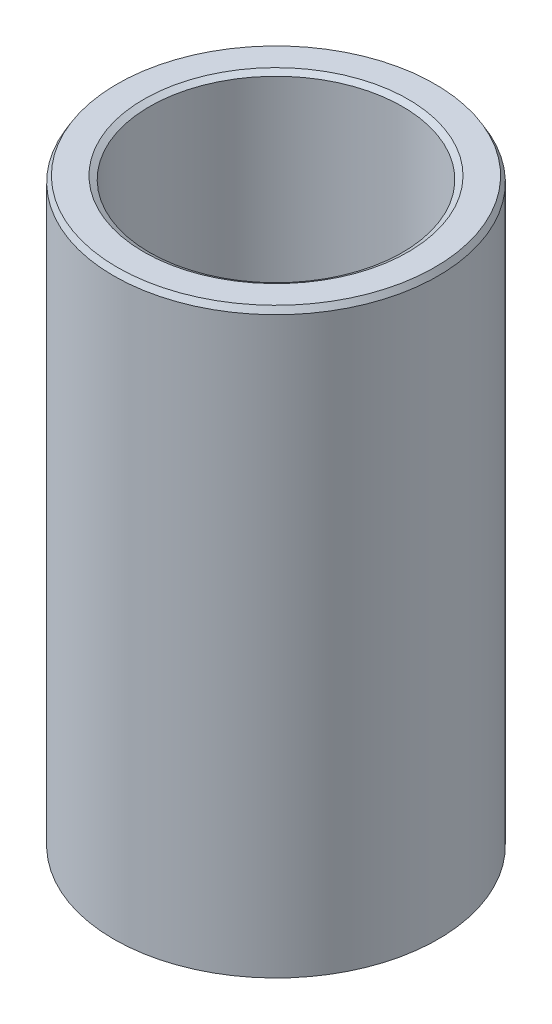
SolidWorks part; units mm, degrees
ref_plane "Front Plane" through (0, 0, 0) normal (0, 0, 1) x (1, 0, 0)
ref_plane "Top Plane" through (0, 0, 0) normal (0, 1, 0) x (1, 0, 0)
ref_plane "Right Plane" through (0, 0, 0) normal (1, 0, 0) x (0, 0, -1)
sketch "Sketch1" plane through (0, 0, 0) normal (0, 1, 0) x (1, 0, 0)
  circle A0 centre (0, 0) radius 47.5
  dimension "SLEEVE_OD" = 95
extrude "Boss-Extrude1" add sketch "Sketch1" along normal blind 170.9189
sketch "Sketch2" plane through (0, 0, 0) normal (0, 1, 0) x (1, 0, 0)
  circle A0 centre (0, 0) radius 37.0365
  dimension "BORE_D" = 74.073
extrude "Cut-Extrude1" cut sketch "Sketch2" along normal through all
chamfer "Chamfer1" distance 1.7006 angle 30 4 edges at (0, 170.9189, 37.0365) (0, 0, 37.0365) (0, 0, 47.5) (0, 170.9189, 47.5) first distance on face at (0, 170.9189, 37.0365) first distance on face at (0, 0, 37.0365) first distance on face at (0, 170.9189, 47.5)
